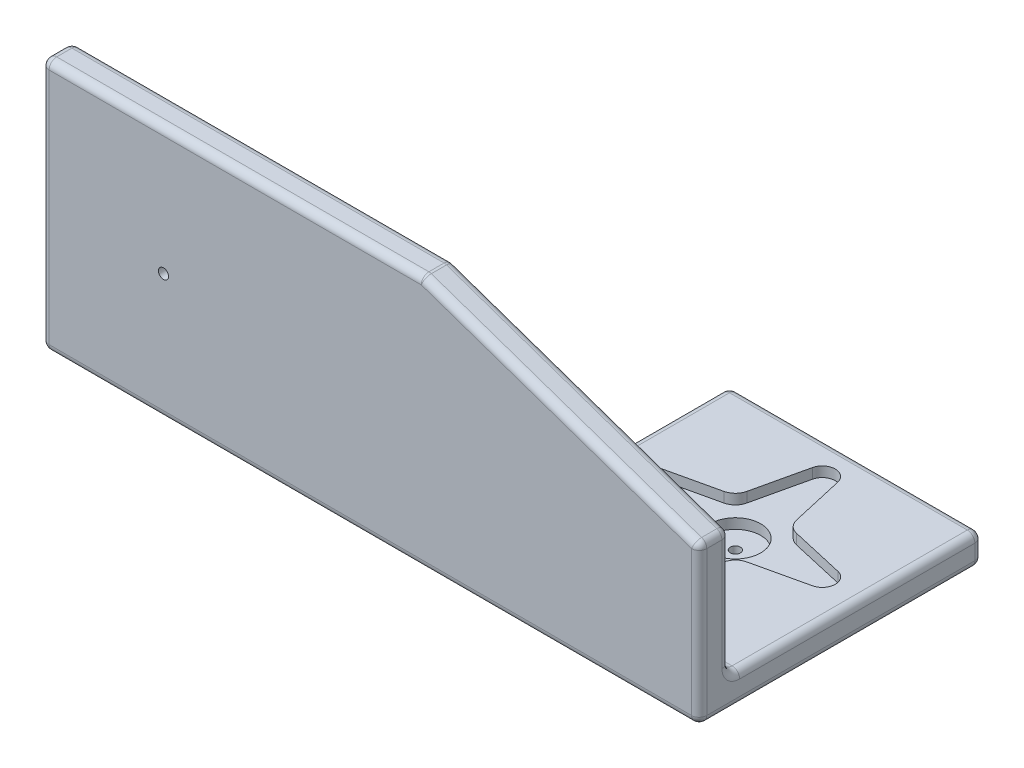
SolidWorks part; units mm, degrees
ref_plane "Plan de face" through (0, 0, 0) normal (0, 0, 1) x (1, 0, 0)
ref_plane "Plan de dessus" through (0, 0, 0) normal (0, 1, 0) x (1, 0, 0)
ref_plane "Plan de droite" through (0, 0, 0) normal (1, 0, 0) x (0, 0, -1)
sketch "Esquisse1" plane through (0, 0, 0) normal (0, 0, 1) x (1, 0, 0)
  line L0 (-35.3226, 27.7016) -> (-35.3226, -22.2984)
  line L1 (-35.3226, -22.2984) -> (94.6774, -22.2984)
  line L2 (94.6774, -22.2984) -> (94.6774, 27.7016)
  line L3 (94.6774, 27.7016) -> (-35.3226, 27.7016)
  dimension "D1" = 50
  dimension "D2" = 130
extrude "Boss.-Extru.1" add sketch "Esquisse1" along normal blind 6
sketch "Esquisse2" plane through (0, 0, 0) normal (0, 0, 1) x (1, 0, 0)
  line L0 (-17.5527, -7.2984) -> (-31.6027, -7.2984) construction
  line L1 (-31.6996, -4.7984) -> (-18.7925, -4.2984)
  line L2 (-18.7925, -10.2984) -> (-31.6996, -9.7984)
  line L3 (-35.3226, -22.2984) -> (94.6774, -22.2984) construction
  arc A0 (-18.7925, -10.2984) -> (-18.7925, -4.2984) centre (-17.5527, -7.2984) ccw
  arc A1 (-31.6996, -4.7984) -> (-31.6996, -9.7984) centre (-31.6027, -7.2984) ccw
  point P8 (-14.3067, -7.2984)
  point P9 (-34.1046, -7.2984)
  dimension "D1" = 15
  dimension "D2" = 19.7979
  dimension "D3" = 6
  dimension "D4" = 5
  dimension "D5" = 14.05
extrude "Enlèv. mat.-Extru.1" [suppressed] cut sketch "Esquisse2" along normal blind 2
sketch "Esquisse5" [suppressed] plane through (0, 0, 0) normal (0, 0, -1) x (-1, 0, 0)
  line L2 (34.1046, 12.7016) -> (17.253, 12.7112) construction
  arc A1 (31.6996, 10.2016) -> (31.6996, 15.2016) centre (31.6027, 12.7016) ccw construction
  circle A3 centre (32.3546, 12.7026) radius 0.6
  dimension "D1" = 1.2
  dimension "D2" = 1.75
extrude "Boss.-Extru.2" [suppressed] add sketch "Esquisse5" against normal blind 2
pattern_linear "Répétition linéaire1" [suppressed] count 6 spacing 2 along (1, 0.0006, 0)
pattern_circular "Répétition circulaire1" [suppressed] count 2 over 360
sketch "Esquisse7" plane through (0, 0, 0) normal (0, 0, -1) x (-1, 0, 0)
  line L0 (-44.6774, -22.2984) -> (-44.6774, -16.2984)
  line L1 (35.3226, -22.2984) -> (-94.6774, -22.2984) construction
  line L2 (-44.6774, -16.2984) -> (-94.6774, -16.2984)
  line L3 (-94.6774, -22.2984) -> (-94.6774, 27.7016) construction
  line L4 (-94.6774, -16.2984) -> (-94.6774, -22.2984)
  line L5 (-94.6774, -22.2984) -> (-44.6774, -22.2984)
  dimension "D1" = 50
  dimension "D2" = 6
extrude "Boss.-Extru.3" add sketch "Esquisse7" along normal blind 50
sketch "Esquisse9" plane through (0, 0, 0) normal (0, 0, -1) x (-1, 0, 0)
  line L0 (-94.6774, 8.8314) -> (-94.6774, 27.7016)
  line L1 (-94.6774, -16.2984) -> (-94.6774, 27.7016) construction
  line L2 (-94.6774, 27.7016) -> (-40, 27.7016)
  line L4 (-40, 27.7016) -> (-94.6774, 8.8314)
extrude "Enlèv. mat.-Extru.4" cut sketch "Esquisse9" against normal through all
sketch "Esquisse14" plane through (33.2856, -16.2984, -37.1856) normal (0, 1, 0) x (0, 0, -1)
  line L0 (-11.0281, -36.3918) -> (-28.2065, -36.3918) construction
  line L1 (-28.7763, -33.8918) -> (-11.2264, -29.8918)
  line L2 (-11.2264, -42.8918) -> (-28.7763, -38.8918)
  arc A0 (-11.2264, -42.8918) -> (-11.2264, -29.8918) centre (-11.0281, -36.3918) ccw
  arc A1 (-28.7763, -33.8918) -> (-28.7763, -38.8918) centre (-28.2065, -36.3918) ccw
  point P11 (-4.525, -36.3918)
  dimension "D1" = 6.503
  dimension "D3" = 18
  dimension "D4" = 13
  dimension "D5" = 5
extrude "Enlèv. mat.-Extru.6" cut sketch "Esquisse14" against normal blind 2
pattern_circular "Répétition circulaire4" count 2 over 360 about axis through (69.6774, 0, -26.1575) along (0, 1, 0) of "Enlèv. mat.-Extru.6"
sketch "Esquisse16" plane through (0, -18.2984, 0) normal (0, 1, 0) x (1, 0, 0)
  circle A0 centre (69.6774, 26.1575) radius 1
  dimension "D1" = 2
extrude "Enlèv. mat.-Extru.7" cut sketch "Esquisse16" against normal through all
pattern_circular "Répétition circulaire5" count 2 every 270 about axis through (69.6774, 0, -26.1575) along (0, 1, 0) of "Répétition circulaire4", "Enlèv. mat.-Extru.6"
sketch "Esquisse17" plane through (0, 0, 0) normal (0, 0, -1) x (-1, 0, 0)
  line L0 (11.1801, 2.5574) -> (-5.9984, 2.5574) construction
  line L1 (-6.5682, 5.0574) -> (10.9817, 9.0574)
  line L2 (10.9817, -3.9426) -> (-6.5682, 0.0574)
  arc A0 (10.9817, -3.9426) -> (10.9817, 9.0574) centre (11.1801, 2.5574) ccw
  arc A1 (-6.5682, 5.0574) -> (-6.5682, 0.0574) centre (-5.9984, 2.5574) ccw
  dimension "D1" = 18
  dimension "D2" = 13
  dimension "D3" = 5
extrude "Enlèv. mat.-Extru.8" cut sketch "Esquisse17" against normal blind 2
pattern_circular "Répétition circulaire6" count 2 over 180 about axis through (-11.1801, 2.5574, 0) along (0, 0, 1) of "Enlèv. mat.-Extru.8"
pattern_circular "Répétition circulaire7" count 2 every 270 about axis through (-11.1801, 2.5574, 0) along (0, 0, 1) of "Répétition circulaire6", "Enlèv. mat.-Extru.8"
fillet "Congé4" radius 3 1 edges at (44.6774, -19.2984, 0)
fillet "Congé7" radius 3 4 edges at (64.3471, -17.2984, -20.8272) (75.0077, -17.2984, -20.8272) (75.0077, -17.2984, -31.4878) (64.3471, -17.2984, -31.4878)
fillet "Congé8" radius 2 1 edges at (68.1774, -16.2984, 0)
sketch "Esquisse18" plane through (0, 0, 2) normal (0, 0, -1) x (-1, 0, 0)
  circle A0 centre (11.2158, 2.6508) radius 1
  dimension "D1" = 2
extrude "Enlèv. mat.-Extru.9" cut sketch "Esquisse18" against normal blind 12
fillet "Congé10" radius 2 4 edges at (-16.5104, -2.7729, 1) (-16.5104, 7.8877, 1) (-5.8497, 7.8877, 1) (-5.8497, -2.7729, 1)
fillet "Congé11" radius 1.5 26 edges at (43.6727, -15.8674, -0.7597) (44.6342, -16.2984, -2.4927) (3.1774, -22.2984, 0) (43.7987, -22.2984, -0.8787) (44.6774, -16.2984, -26.5) (44.6774, -22.2984, -26.5) (69.6774, -16.2984, -50) (44.6774, -19.2984, -50) (69.6774, -22.2984, -50) (94.6774, -19.2984, -50) (94.6774, -22.2984, -22) (94.6774, -6.7335, 6) (94.6774, -2.7335, 0) (94.6774, -15.7126, -0.5858) (94.6774, -16.2984, -26) (-35.3226, 2.7016, 6) (-35.3226, -22.2984, 3) (-35.3226, 2.7016, 0) (-35.3226, 27.7016, 3) (2.3387, 27.7016, 0) (2.3387, 27.7016, 6) (94.6774, 8.8314, 3) (67.3387, 18.2665, 6) (40, 27.7016, 3) (67.3387, 18.2665, 0) (29.6774, -22.2984, 6)
sketch "Esquisse19" plane through (0, 0, 2) normal (0, 0, -1) x (-1, 0, 0)
  circle A0 centre (11.2158, 2.6508) radius 5
  dimension "D1" = 10
extrude "Enlèv. mat.-Extru.10" cut sketch "Esquisse19" against normal blind 2
sketch "Esquisse20" plane through (0, -18.2984, 0) normal (0, 1, 0) x (1, 0, 0)
  circle A0 centre (69.6774, 26.1575) radius 5
  dimension "D1" = 10
extrude "Enlèv. mat.-Extru.11" cut sketch "Esquisse20" against normal blind 2
